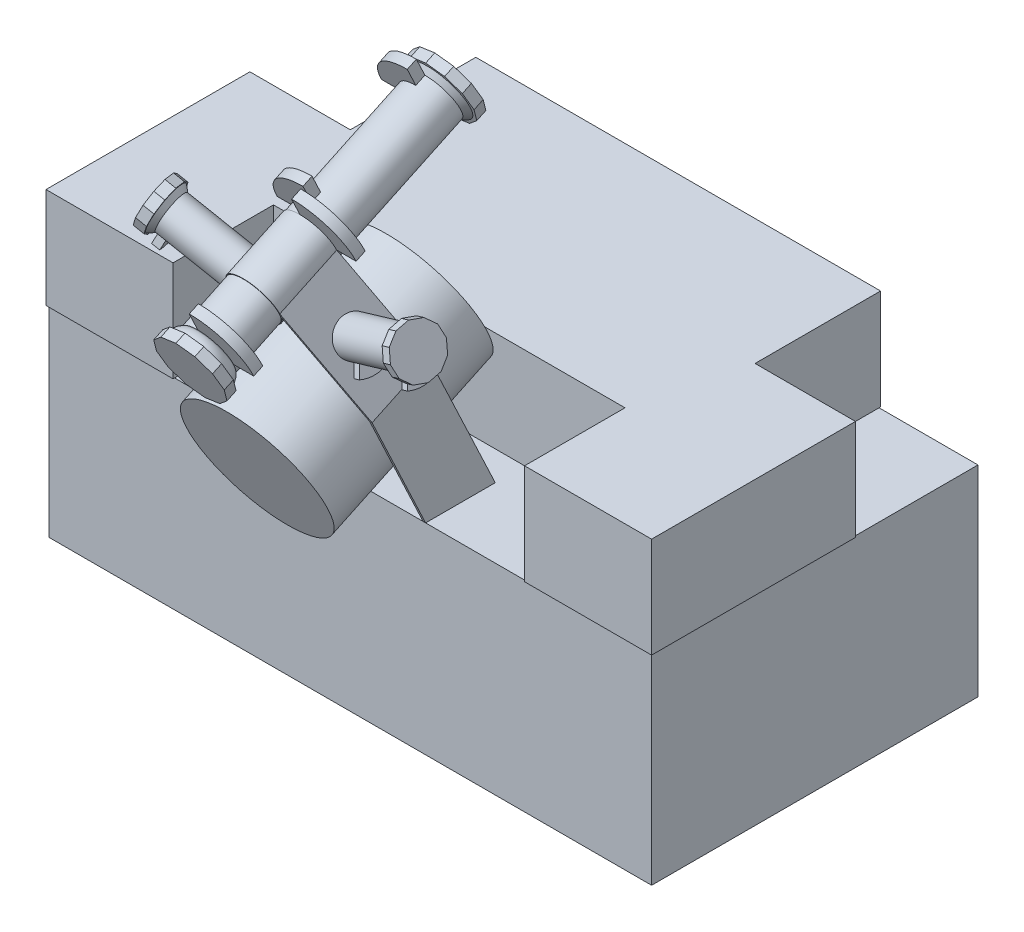
SolidWorks part; units mm, degrees
ref_plane "Front Plane" through (0, 0, 0) normal (0, 0, 1) x (1, 0, 0)
ref_plane "Top Plane" through (0, 0, 0) normal (0, 1, 0) x (1, 0, 0)
ref_plane "Right Plane" through (0, 0, 0) normal (1, 0, 0) x (0, 0, -1)
sketch "Sketch1" plane through (0, 0, 0) normal (0, 1, 0) x (1, 0, 0)
  line L1 (-60, 32.5) -> (60, 32.5)
  line L2 (-60, 32.5) -> (-60, -32.5)
  line L3 (-60, -32.5) -> (60, -32.5)
  line L4 (60, 32.5) -> (60, -32.5)
  line L5 (-60, 32.5) -> (60, -32.5) construction
  line L6 (-60, -32.5) -> (60, 32.5) construction
  point P0 (0, 0)
  dimension "D1" = 120
  dimension "D2" = 65
extrude "Boss-Extrude1" add sketch "Sketch1" along normal blind 40
sketch "Sketch2" plane through (0, 40, 0) normal (0, 1, 0) x (1, 0, 0)
  line L0 (60, 32.5) -> (-60, 32.5) construction
  line L1 (-40.3, 32.8) -> (40.3, 32.8)
  line L2 (-60.3, 7.8) -> (-60.3, -32.8)
  line L3 (-60.3, -32.8) -> (-35, -32.8)
  line L4 (60.3, 7.8) -> (60.3, -32.8)
  line L5 (35, -32.8) -> (60.3, -32.8)
  line L6 (60, -32.5) -> (60, 32.5) construction
  line L7 (-60, 32.5) -> (-60, -32.5) construction
  line L8 (0, -12.8) -> (0, 32.6) construction
  line L9 (-60, -32.5) -> (60, -32.5) construction
  line L12 (-60.3, 7.8) -> (-40.3, 7.8)
  line L13 (-40.3, 32.8) -> (-40.3, 7.8)
  line L16 (78.6099, 57.6) -> (38.6099, 57.6)
  line L18 (60.3, 7.8) -> (40.3, 7.8)
  line L19 (40.3, 32.8) -> (40.3, 7.8)
  line L23 (-35, -32.8) -> (-35, -12.8)
  line L24 (-35, -12.8) -> (35, -12.8)
  line L25 (35, -32.8) -> (35, -12.8)
  point P0 (0, 0)
  dimension "D1" = 0.3
  dimension "D2" = 0.3
  dimension "D3" = 25
  dimension "D4" = 20
  dimension "D5" = 20
  dimension "D6" = 25
  dimension "D7" = 70
  dimension "D8" = 20
  dimension "D9" = 0.3
  dimension "D10" = 0.3
extrude "Boss-Extrude3" add sketch "Sketch2" along normal blind 20 contours L1 L19 L18 L4 L5 L25 L24 L23 L3 L2 L12 L13
ref_plane "Plane1" through (0, 0, 0) normal (-1, 0, 0) x (0, 0, 1)
sketch "Sketch3" plane through (0, 0, 0) normal (-1, 0, 0) x (0, 0, 1)
  line L0 (32.5, 40) -> (43.1625, 62.6122)
  line L1 (43.1625, 62.6122) -> (29.2974, 62.6122)
  line L4 (18.6349, 40) -> (32.5, 40)
  line L5 (29.2974, 62.6122) -> (18.6349, 40)
  dimension "D1" = 25
extrude "Boss-Extrude4" add sketch "Sketch3" along normal blind 15 and the other way blind 15
sketch "Sketch4" plane through (0, -5.2612, 11.1577) normal (0, -0.4265, 0.9045) x (1, 0, 0)
  line L0 (0, 95.0407) -> (0, 75.0407) construction
  line L1 (15, 75.0407) -> (-15, 75.0407) construction
  line L2 (-15, 75.0407) -> (-5.1445, 95.0407)
  line L3 (5.1445, 95.0407) -> (15, 75.0407)
  line L4 (-15, 75.0407) -> (15, 75.0407)
  circle A0 centre (0, 95.0407) radius 5.1445
  dimension "D1" = 20
extrude "Boss-Extrude5" add sketch "Sketch4" against normal up to surface (12.5408 mm away) separate body
sketch "Sketch5" plane through (-15, 0, 0) normal (-1, 0, 0) x (0, 0, 1)
  line L0 (43.1625, 62.6122) -> (31.8195, 67.9608)
  line L1 (31.8195, 67.9608) -> (29.2974, 62.6122)
  line L2 (29.2974, 62.6122) -> (43.1625, 62.6122)
extrude "Boss-Extrude6" add sketch "Sketch5" against normal up to surface (30 mm away) contours L1 L2 L0 up to face at (15, 51.3061, 30.8987)
sketch "Sketch6" plane through (0, -5.2612, 11.1577) normal (0, -0.4265, 0.9045) x (1, 0, 0)
  line L0 (-14.5, 50.0407) -> (-14.5, 74.946)
  line L1 (15, 50.0407) -> (-15, 50.0407) construction
  line L2 (-14.5, 74.946) -> (-5.0588, 94.1053)
  line L5 (14.5, 50.0407) -> (-14.5, 50.0407)
  line L6 (-15, 50.0407) -> (-15, 75.0407) construction
  line L7 (-15, 75.0407) -> (-5.1445, 95.0407) construction
  line L9 (5.0561, 94.0911) -> (14.5, 74.946)
  line L10 (14.5, 74.946) -> (14.5, 50.0407)
  arc A0 (-5.0588, 94.1053) -> (5.0561, 94.0911) centre (0, 95.0407) ccw
  arc A1 (5.1445, 95.0407) -> (-5.1445, 95.0407) centre (0, 95.0407) ccw construction
  dimension "D1" = 0.5
extrude "Cut-Extrude1" cut sketch "Sketch6" against normal up to surface (12.5408 mm away) up to face at (0, 65.446, 30.6336)
sketch "Sketch7" plane through (0, 0, 12.8) normal (0, 0, 1) x (1, 0, 0)
  line L1 (-14.5, 40) -> (14.5, 40)
  line L2 (-14.5, 40) -> (-14.5, 45.3487)
  line L3 (-14.5, 45.3487) -> (14.5, 45.3487)
  line L4 (14.5, 40) -> (14.5, 45.3487)
extrude "Cut-Extrude2" cut sketch "Sketch7" along normal up to surface (19.7 mm away) up to face at (0, 32, 32.5)
sketch "Sketch8" plane through (0, -5.2612, 11.1577) normal (0, -0.4265, 0.9045) x (1, 0, 0)
  circle A0 centre (0, 95.0407) radius 5
extrude "Boss-Extrude7" add sketch "Sketch8" along normal blind 10 and the other way blind 40
ref_plane "Plane2" through (0, -9.9527, 21.107) normal (0, -0.4265, 0.9045) x (1, 0, 0)
sketch "Sketch9" plane through (0, -9.9527, 21.107) normal (0, -0.4265, 0.9045) x (1, 0, 0)
  circle A0 centre (0, 95.0407) radius 6
loft "Loft1" add profiles "Sketch9" section "Sketch9" section edge at (0, 71.9145, 58.6049) connector at (-5.2432, 78.6488, 62.8859) connector at (-4.3416, 78.6801, 61.7951)
sketch "Sketch10" plane through (0, -9.9527, 21.107) normal (0, -0.4265, 0.9045) x (1, 0, 0)
  circle A0 centre (0, 95.0407) radius 6
extrude "Boss-Extrude8" add sketch "Sketch10" along normal blind 1
fillet "Fillet1" radius 3 1 edges at (0, 70.5835, 59.0828)
sketch "Sketch13" plane through (0, -10.3792, 22.0115) normal (0, -0.4265, 0.9045) x (1, 0, 0)
  line L1 (0, 88.2793) -> (3.3807, 89.1851)
  line L2 (3.3807, 89.1851) -> (5.8556, 91.66)
  line L3 (5.8556, 91.66) -> (6.7615, 95.0407)
  line L4 (6.7615, 95.0407) -> (5.8556, 98.4215)
  line L5 (5.8556, 98.4215) -> (3.3807, 100.8964)
  line L6 (3.3807, 100.8964) -> (0, 101.8022)
  line L7 (0, 101.8022) -> (-3.3807, 100.8964)
  line L8 (-3.3807, 100.8964) -> (-5.8556, 98.4215)
  line L9 (-5.8556, 98.4215) -> (-6.7615, 95.0407)
  line L10 (-6.7615, 95.0407) -> (-5.8556, 91.66)
  line L11 (-5.8556, 91.66) -> (-3.3807, 89.1851)
  line L12 (-3.3807, 89.1851) -> (0, 88.2793)
  circle A0 centre (0, 95.0407) radius 6.5311 construction
  dimension "D1" = 3.5
extrude "Boss-Extrude10" add sketch "Sketch13" along normal blind 2
sketch "Sketch14" plane through (0, -5.2612, 11.1577) normal (0, -0.4265, 0.9045) x (1, 0, 0)
  line L0 (0, 88.2793) -> (0, 50.0407) construction
  line L1 (-14.5, 50.0407) -> (14.5, 50.0407) construction
  circle A0 centre (0, 68.0407) radius 14.1
  dimension "D1" = 18
extrude "Boss-Extrude11" add sketch "Sketch14" along normal up to surface (12 mm away) and the other way blind 23 separate body up to face at (0, 70.157, 59.9873)
sketch "Sketch15" plane through (41.8225, 18.6406, 8.7897) normal (0.897, 0.3998, 0.1885) x (0.1718, 0.0777, -0.9821)
  line L0 (-37.8346, 74.0992) -> (-29.17, 53.5552) construction
  line L1 (-32.057, 76.5359) -> (-43.6122, 71.6624) construction
  line L2 (-23.3925, 55.9919) -> (-34.9476, 51.1184) construction
  circle A0 centre (-33.5023, 63.8272) radius 3.6
extrude "Boss-Extrude12" add sketch "Sketch15" along normal blind 15
ref_plane "Plane3" through (56.1746, 25.0375, 11.8061) normal (0.897, 0.3998, 0.1885) x (0.1718, 0.0777, -0.9821)
sketch "Sketch16" plane through (56.1746, 25.0375, 11.8061) normal (0.897, 0.3998, 0.1885) x (0.1718, 0.0777, -0.9821)
  circle A0 centre (-33.5023, 63.8272) radius 4.5
loft "Loft2" add profiles "Sketch16" section "Sketch16" section face at (22.0618, 83.6166, 44.5838) connector at (23.1176, 81.6797, 48.972) connector at (22.5808, 80.8315, 48.0205)
sketch "Sketch17" plane through (56.1746, 25.0375, 11.8061) normal (0.897, 0.3998, 0.1885) x (0.1718, 0.0777, -0.9821)
  line L0 (-33.5023, 68.3272) -> (-33.5023, 59.3272) construction
  line L1 (-33.5023, 58.9975) -> (-31.0875, 59.6446)
  line L2 (-31.0875, 59.6446) -> (-29.3197, 61.4124)
  line L3 (-29.3197, 61.4124) -> (-28.6727, 63.8272)
  line L4 (-28.6727, 63.8272) -> (-29.3197, 66.242)
  line L5 (-29.3197, 66.242) -> (-31.0875, 68.0098)
  line L6 (-31.0875, 68.0098) -> (-33.5023, 68.6568)
  line L7 (-33.5023, 68.6568) -> (-35.9171, 68.0098)
  line L8 (-35.9171, 68.0098) -> (-37.6849, 66.242)
  line L9 (-37.6849, 66.242) -> (-38.3319, 63.8272)
  line L10 (-38.3319, 63.8272) -> (-37.6849, 61.4124)
  line L11 (-37.6849, 61.4124) -> (-35.9171, 59.6446)
  line L12 (-35.9171, 59.6446) -> (-33.5023, 58.9975)
  circle A0 centre (-33.5023, 63.8272) radius 4.6651 construction
  circle A1 centre (-33.5023, 63.8272) radius 4.5 construction
  point P20 (-33.5023, 63.8272)
  dimension "D1" = 2.5
extrude "Boss-Extrude13" add sketch "Sketch17" along normal blind 2
sketch "Sketch18" plane through (41.8225, 18.6406, 8.7897) normal (0.897, 0.3998, 0.1885) x (0.1722, 0.0767, -0.9821)
  line L0 (-33.5731, 63.8044) -> (-33.5731, 63.7939) construction
  line L5 (-33.5731, 63.7939) -> (-33.5694, 63.7955) construction
  line L6 (-33.5677, 63.7915) -> (-33.5731, 63.8044) construction
  line L7 (-33.5731, 63.7939) -> (-35.6324, 58.1584)
  line L8 (-33.5731, 63.7939) -> (-28.095, 61.3465)
  arc A0 (-35.6324, 58.1584) -> (-28.095, 61.3465) centre (-33.5731, 63.7939) ccw
  dimension "D2" = 47
extrude "Boss-Extrude14" add sketch "Sketch18" along normal blind 1.5 contours L8 A0 L7
ref_plane "Plane4" through (55.2776, 24.6377, 11.6176) normal (0.897, 0.3998, 0.1885) x (0.1718, 0.0777, -0.9821)
sketch "Sketch19" plane through (55.2776, 24.6377, 11.6176) normal (0.897, 0.3998, 0.1885) x (0.1718, 0.0777, -0.9821)
  line L0 (-31.1757, 58.3001) -> (-33.5073, 63.8285) construction
  line L1 (-33.5073, 63.8285) -> (-35.5724, 58.1951)
  line L2 (-33.5073, 63.8285) -> (-28.0317, 61.3755)
  arc A0 (-35.5724, 58.1951) -> (-28.0317, 61.3755) centre (-33.5073, 63.8285) ccw construction
  arc A1 (-35.5724, 58.1951) -> (-28.0317, 61.3755) centre (-33.5073, 63.8285) ccw
extrude "Boss-Extrude15" add sketch "Sketch19" against normal blind 1.5
ref_plane "Plane5" through (0, 0, 0) normal (1, 0, 0) x (0, 0, -1)
mirror "Mirror2" about plane through (0, 0, 0) normal (1, 0, 0) of bodies 119
ref_plane "Plane7" through (0, 12.2252, -25.9263) normal (0, 0.4265, -0.9045) x (-1, 0, 0)
sketch "Sketch20" plane through (0, 12.2252, -25.9263) normal (0, 0.4265, -0.9045) x (-1, 0, 0)
  circle A0 centre (0, 95.0407) radius 6
  circle A1 centre (0, 95.0407) radius 6 construction
sketch "Sketch22" plane through (0, 11.7987, -25.0219) normal (0, 0.4265, -0.9045) x (-1, 0, 0)
  line L0 (0, 104.0407) -> (0, 95.0407)
  line L1 (0, 95.0407) -> (9, 95.0407)
  arc A0 (9, 95.0407) -> (0, 104.0407) centre (0, 95.0407) ccw
  dimension "D1" = 9
  dimension "D2" = 9
extrude "Boss-Extrude17" add sketch "Sketch22" against normal blind 2
sketch "Sketch23" plane through (0, 11.7987, -25.0219) normal (0, 0.4265, -0.9045) x (-1, 0, 0)
  circle A0 centre (0, 95.0407) radius 5
loft "Loft5" add profiles "Sketch23", "Sketch20" connector at (4.9998, 97.7193, 15.4929) connector at (5.9938, 98.4347, 14.7246)
sketch "Sketch24" plane through (0, 12.2252, -25.9263) normal (0, 0.4265, -0.9045) x (-1, 0, 0)
  line L1 (0, 88.2793) -> (3.3807, 89.1851)
  line L2 (3.3807, 89.1851) -> (5.8556, 91.66)
  line L3 (5.8556, 91.66) -> (6.7615, 95.0407)
  line L4 (6.7615, 95.0407) -> (5.8556, 98.4215)
  line L5 (5.8556, 98.4215) -> (3.3807, 100.8964)
  line L6 (3.3807, 100.8964) -> (0, 101.8022)
  line L7 (0, 101.8022) -> (-3.3807, 100.8964)
  line L8 (-3.3807, 100.8964) -> (-5.8556, 98.4215)
  line L9 (-5.8556, 98.4215) -> (-6.7615, 95.0407)
  line L10 (-6.7615, 95.0407) -> (-5.8556, 91.66)
  line L11 (-5.8556, 91.66) -> (-3.3807, 89.1851)
  line L12 (-3.3807, 89.1851) -> (0, 88.2793)
  circle A0 centre (0, 95.0407) radius 6.5311 construction
extrude "Boss-Extrude18" add sketch "Sketch24" along normal blind 2
sketch "Sketch25" plane through (0, 0.0874, -0.1854) normal (0, 0.4265, -0.9045) x (-1, 0, 0)
  line L0 (0, 104.0407) -> (0, 95.0407)
  line L1 (0, 95.0407) -> (-9, 95.0407)
  arc A0 (0, 104.0407) -> (-9, 95.0407) centre (0, 95.0407) ccw
extrude "Boss-Extrude19" add sketch "Sketch25" along normal blind 2
ref_plane "Plane8" through (0, 1.1537, -2.4466) normal (0, 0.4265, -0.9045) x (-1, 0, 0)
sketch "Sketch26" plane through (0, 1.1537, -2.4466) normal (0, 0.4265, -0.9045) x (-1, 0, 0)
  line L0 (9, 95.0407) -> (0, 95.0407)
  line L1 (0, 95.0407) -> (0, 104.0407)
  arc A0 (9, 95.0407) -> (0, 104.0407) centre (0, 95.0407) ccw
extrude "Boss-Extrude20" add sketch "Sketch26" along normal blind 2
ref_plane "Plane9" through (0, -9.5262, 20.2025) normal (0, -0.4265, 0.9045) x (1, 0, 0)
sketch "Sketch27" plane through (0, -9.5262, 20.2025) normal (0, -0.4265, 0.9045) x (1, 0, 0)
  line L0 (0, 95.0407) -> (0, 104.0407)
  line L1 (0, 95.0407) -> (9, 95.0407)
  arc A0 (9, 95.0407) -> (0, 104.0407) centre (0, 95.0407) ccw
extrude "Boss-Extrude21" add sketch "Sketch27" against normal blind 2
